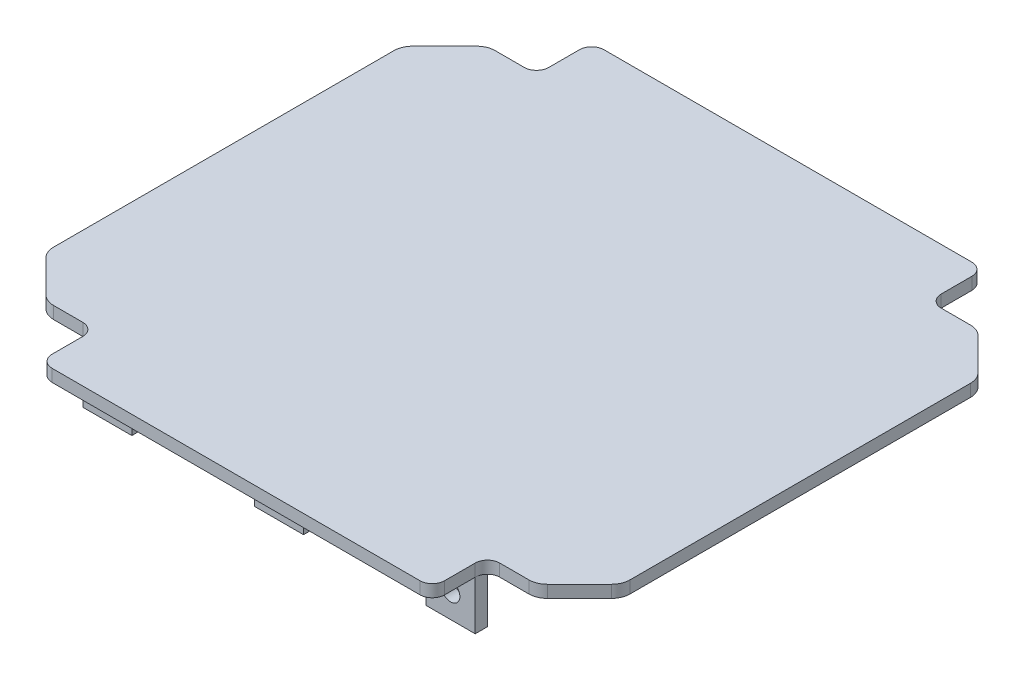
SolidWorks part; units mm, degrees
ref_plane "Front Plane" through (0, 0, 0) normal (0, 0, 1) x (1, 0, 0)
ref_plane "Top Plane" through (0, 0, 0) normal (0, 1, 0) x (1, 0, 0)
ref_plane "Right Plane" through (0, 0, 0) normal (1, 0, 0) x (0, 0, -1)
sketch "Эскиз1" plane through (0, 0, 0) normal (0, 1, 0) x (1, 0, 0)
  line L1 (-47, -36) -> (47, -36)
  line L2 (-47, -36) -> (-47, 36)
  line L3 (-47, 36) -> (47, 36)
  line L4 (47, -36) -> (47, 36)
  line L5 (-47, -36) -> (47, 36) construction
  line L6 (-47, 36) -> (47, -36) construction
  point P0 (0, 0)
  dimension "D1" = 94
  dimension "D2" = 72
extrude "Бобышка-Вытянуть1" add sketch "Эскиз1" along normal blind 2
sketch "Эскиз2" plane through (0, 0, 36) normal (0, 0, 1) x (1, 0, 0)
  line L0 (-47, 2) -> (47, 2) construction
  line L1 (-32, 2) -> (-24, 2)
  line L2 (-32, 2) -> (-32, -8)
  line L3 (-32, -8) -> (-24, -8)
  line L4 (-24, 2) -> (-24, -8)
  line L5 (-47, 2) -> (-47, 0) construction
  line L6 (-47, 0) -> (47, 0) construction
  line L8 (24, 2) -> (32, 2)
  line L9 (24, 2) -> (24, -8)
  line L10 (24, -8) -> (32, -8)
  line L11 (32, 2) -> (32, -8)
  line L12 (47, 2) -> (47, 0) construction
  line L13 (-4, 2) -> (4, 2)
  line L14 (-4, 2) -> (-4, -8)
  line L15 (-4, -8) -> (4, -8)
  line L16 (4, 2) -> (4, -8)
  dimension "D1" = 8
  dimension "D2" = 15
  dimension "D3" = 8
  dimension "D4" = 15
  dimension "D5" = 8
  dimension "D6" = 8
  dimension "D7" = 20
  dimension "D8" = 8
  dimension "D9" = 10
extrude "Бобышка-Вытянуть2" add sketch "Эскиз2" along normal blind 2
fillet "Скругление4" radius 2 6 edges at (-24, 1, 36) (32, 1, 36) (4, 1, 36) (24, 1, 36) (-4, 1, 36) (-32, 1, 36)
mirror "Зеркальное отражение1" about plane through (0, 0, 0) normal (0, 0, 1) of "Бобышка-Вытянуть2"
fillet "Скругление5" radius 2 6 edges at (24, 1, -36) (-4, 1, -36) (-32, 1, -36) (-24, 1, -36) (4, 1, -36) (32, 1, -36)
sketch "Эскиз3" plane through (0, 0, -38) normal (0, 0, -1) x (-1, 0, 0)
  line L0 (-24, -8) -> (-32, -8) construction
  line L1 (-24, 0) -> (-24, -8) construction
  line L2 (4, -8) -> (-4, -8) construction
  line L3 (4, 0) -> (4, -8) construction
  line L4 (24, -8) -> (24, 0) construction
  line L5 (32, -8) -> (24, -8) construction
  circle A0 centre (-28, -4) radius 1.5
  circle A1 centre (0, -4) radius 1.5
  circle A2 centre (28, -4) radius 1.5
  dimension "D1" = 3
  dimension "D4" = 3
  dimension "D5" = 3
  dimension "D2" = 4
  dimension "D3" = 4
  dimension "D6" = 4
  dimension "D7" = 4
  dimension "D8" = 4
  dimension "D9" = 4
extrude "Вырез-Вытянуть1" cut sketch "Эскиз3" against normal through all
sketch "Эскиз4" plane through (0, 0, 0) normal (0, 0, -1) x (-1, 0, 0)
  line L0 (-32, 2) -> (-24, 2) construction
  line L1 (-32, 2) -> (32, 2)
  line L2 (-32, 2) -> (-32, 0)
  line L3 (-32, 0) -> (32, 0)
  line L4 (32, 2) -> (32, 0)
  line L5 (-32, 2) -> (32, 0) construction
  line L6 (-32, 0) -> (32, 2) construction
  point P0 (0, 1)
extrude "Бобышка-Вытянуть3" add sketch "Эскиз4" along normal mid plane 90
fillet "Скругление6" radius 2 4 edges at (32, 1, 45) (-32, 1, 45) (-32, 1, -45) (32, 1, -45)
fillet "Congé2" radius 2 4 edges at (-47, 1, 36) (-47, 1, -36) (47, 1, -36) (47, 1, 36)
sketch "Esquisse1" plane through (0, 2, 0) normal (0, 1, 0) x (1, 0, 0)
  line L1 (45, 36) -> (34, 36) construction
  line L2 (47, -34) -> (47, 34) construction
  line L3 (34, -36) -> (45, -36) construction
  line L4 (-45, -36) -> (-34, -36) construction
  line L5 (-34, 36) -> (-45, 36) construction
  line L6 (-47, 34) -> (-47, -34) construction
  line L7 (45, 36) -> (34, 36) construction
  line L15 (47, -34) -> (47, 34) construction
  line L16 (34, -36) -> (45, -36) construction
  line L17 (-45, -36) -> (-34, -36) construction
  line L18 (-34, 36) -> (-45, 36) construction
  line L19 (-47, 34) -> (-47, -34) construction
  line L20 (-47, -29) -> (-40, -36)
  line L21 (-47, -29) -> (-47, -36)
  line L22 (-47, -36) -> (-40, -36)
  line L23 (-47, 0) -> (47, 0) construction
  line L24 (0, 45) -> (0, -45) construction
  line L25 (-47, 36) -> (-40, 36)
  line L26 (-30, 45) -> (30, 45) construction
  line L27 (-30, -45) -> (30, -45) construction
  line L28 (-47, 29) -> (-47, 36)
  line L29 (-47, 29) -> (-40, 36)
  line L30 (47, -29) -> (47, -36)
  line L31 (47, -29) -> (40, -36)
  line L32 (47, -36) -> (40, -36)
  line L33 (47, 29) -> (47, 36)
  line L34 (47, 29) -> (40, 36)
  line L35 (47, 36) -> (40, 36)
  dimension "D1" = 7
  dimension "D2" = 7
extrude "Enlèv. mat.-Extru.1" cut sketch "Esquisse1" against normal through all
fillet "Congé3" radius 3 8 edges at (40, 1, 36) (47, 1, 29) (47, 1, -29) (40, 1, -36) (-40, 1, -36) (-47, 1, -29) (-47, 1, 29) (-40, 1, 36)
